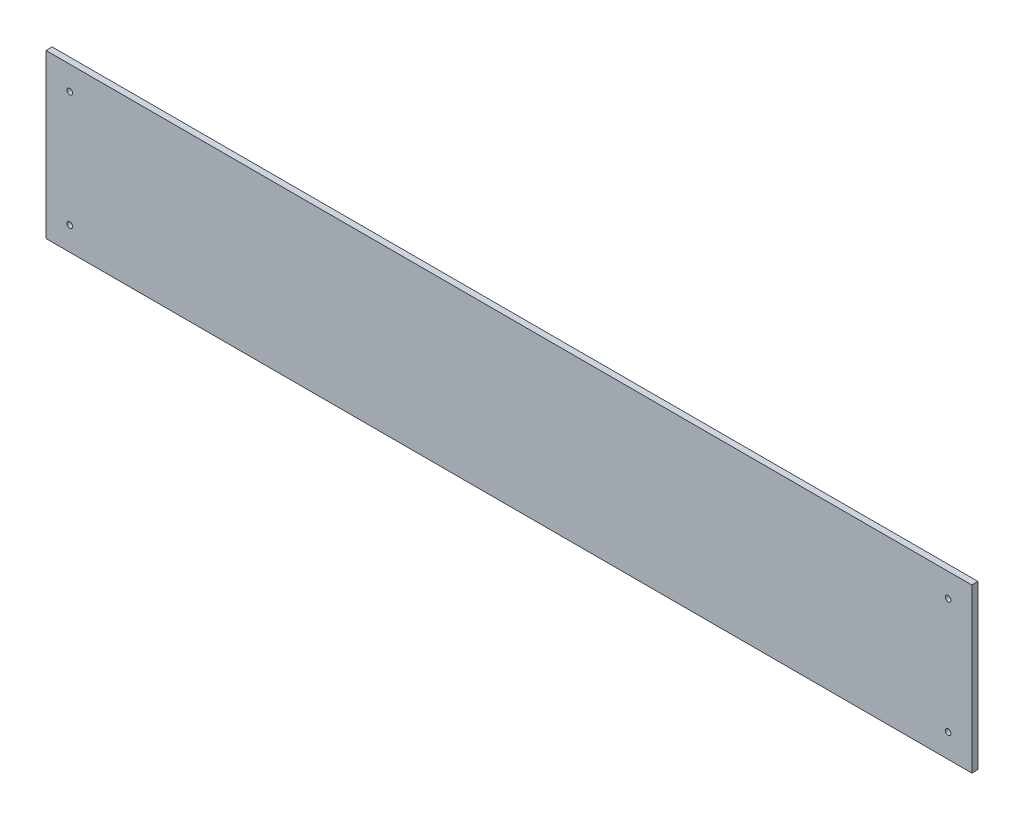
SolidWorks part; units mm, degrees
ref_plane "Piano frontale" through (0, 0, 0) normal (0, 0, 1) x (1, 0, 0)
ref_plane "Piano superiore" through (0, 0, 0) normal (0, 1, 0) x (1, 0, 0)
ref_plane "Piano destro" through (0, 0, 0) normal (1, 0, 0) x (0, 0, -1)
sketch "f" plane through (0, 0, 0) normal (0, 0, 1) x (1, 0, 0)
  line L0 (0, 0) -> (0, 79)
  line L1 (0, 79) -> (449, 79)
  line L2 (449, 79) -> (449, 0)
  line L3 (449, 0) -> (0, 0)
  line L4 (0, 39.5) -> (449, 39.5) construction
  line L5 (224.5, 42) -> (224.5, 123.488) construction
  line L10 (449, 79) -> (224.5, 0) construction
  line L11 (334, 39.5) -> (334, 81.5) construction
  line L12 (224.5, 0) -> (0, 79) construction
  line L13 (112.25, 42) -> (112.25, 84) construction
  circle A0 centre (11.5, 67.5) radius 1.3617
  circle A1 centre (437.5, 67.5) radius 1.3617
  circle A2 centre (11.5, 11.5) radius 1.3617
  circle A3 centre (437.5, 11.5) radius 1.3617
  dimension "D3" = 11.5
  dimension "D4" = 11.5
  dimension "D1" = 79
  dimension "D2" = 449
extrude "Estrusione-Estrusione1" add sketch "f" along normal blind 3
